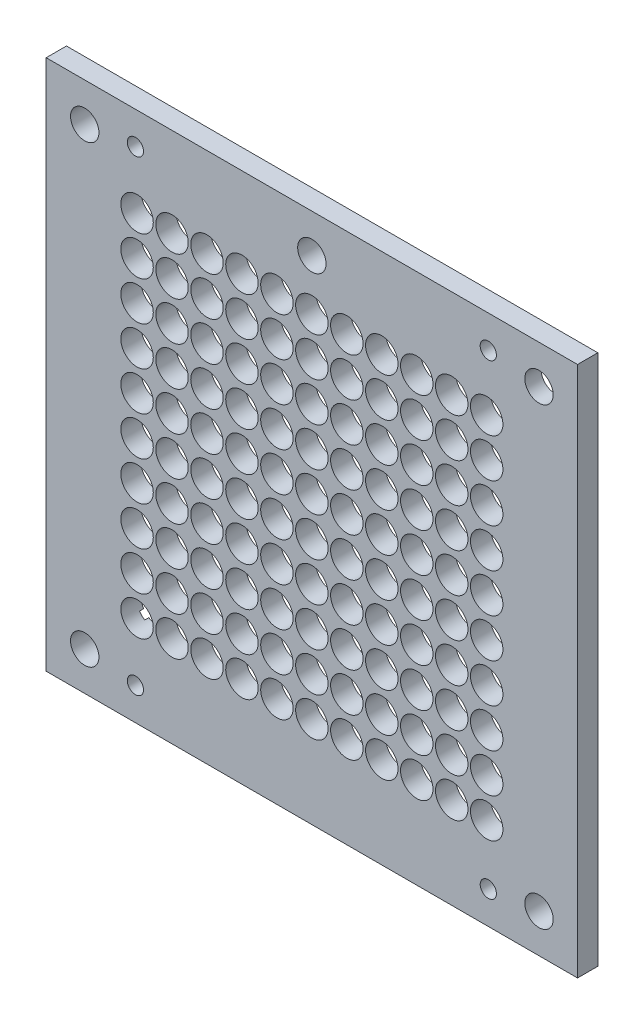
SolidWorks part; units mm, degrees
ref_plane "Ebene vorne" through (0, 0, 0) normal (0, 0, 1) x (1, 0, 0)
ref_plane "Ebene oben" through (0, 0, 0) normal (0, 1, 0) x (1, 0, 0)
ref_plane "Ebene rechts" through (0, 0, 0) normal (1, 0, 0) x (0, 0, -1)
sketch "Skizze2" plane through (0, 0, 0) normal (0, 0, 1) x (1, 0, 0)
  line L0 (-65.5, 65.5) -> (-65.5, -65.5) construction
  line L1 (-65.5, -65.5) -> (65.5, -65.5) construction
  line L2 (65.5, 65.5) -> (-65.5, 65.5) construction
  line L3 (65.5, -65.5) -> (65.5, 65.5) construction
  line L4 (-65.5, 65.5) -> (-65.5, -65.5)
  line L5 (-65.5, -65.5) -> (65.5, -65.5)
  line L6 (65.5, 65.5) -> (-65.5, 65.5)
  line L7 (65.5, -65.5) -> (65.5, 65.5)
extrude "Aufsatz-Linear austragen1" add sketch "Skizze2" along normal blind 5
sketch "Skizze3" plane through (0, 0, 0) normal (0, 0, -1) x (-1, 0, 0)
  line L0 (0, 65.5) -> (0, 0) construction
  line L1 (-65.5, 65.5) -> (65.5, 65.5) construction
  line L2 (-67.5, 67.5) -> (67.5, 67.5) construction
  circle A0 centre (0, 56) radius 3.5
  dimension "D1" = 7
  dimension "D2" = 11.5
extrude "Schnitt-Linear austragen1" cut sketch "Skizze3" against normal up to surface (5 mm away) up to face at (0, 0, 5)
sketch "Skizze4" plane through (0, 0, 0) normal (0, 0, -1) x (-1, 0, 0)
  line L0 (0, 0) -> (0, 65.5) construction
  line L1 (-65.5, 65.5) -> (65.5, 65.5) construction
  line L2 (-67.5, 67.5) -> (67.5, 67.5) construction
  circle A0 centre (0, 43.5) radius 4
  dimension "D1" = 8
  dimension "D2" = 24
extrude "Schnitt-Linear austragen2" cut sketch "Skizze4" against normal up to surface (5 mm away) up to face at (3.5, 56, 5)
pattern_linear "Lineares Muster1" count 6 spacing 8.62 along (1, 0, 0) count 10 spacing 9.6111 along (0, -1, 0) of "Schnitt-Linear austragen2"
pattern_linear "Lineares Muster2" count 6 spacing 8.62 along (-1, 0, 0) count 10 spacing 9.6111 along (0, -1, 0) skipping (0, 1), (0, 2), (0, 3), (0, 4), (0, 5), (0, 6), (0, 7), (0, 8), (0, 9) of "Schnitt-Linear austragen2"
sketch "Skizze5" plane through (0, 0, 0) normal (0, 0, -1) x (-1, 0, 0)
  line L0 (-67.5, -67.5) -> (-67.5, 67.5) construction
  line L1 (-67.5, 67.5) -> (67.5, 67.5) construction
  line L2 (67.5, 67.5) -> (67.5, -67.5) construction
  line L3 (67.5, -67.5) -> (-67.5, -67.5) construction
  circle A0 centre (-50, 50) radius 6
  circle A1 centre (50, 50) radius 6
  circle A2 centre (-50, -50) radius 6
  circle A3 centre (50, -50) radius 6
  dimension "D1" = 12
  dimension "D3" = 17.5
  dimension "D4" = 12
  dimension "D5" = 17.5
  dimension "D6" = 17.5
  dimension "D7" = 12
  dimension "D8" = 12
  dimension "D9" = 17.5
  dimension "D10" = 17.5
  dimension "D11" = 17.5
  dimension "D12" = 17.5
  dimension "D2" = 17.5
extrude "Schnitt-Linear austragen3" cut sketch "Skizze5" against normal blind 1
sketch "Skizze6" plane through (0, 0, 0) normal (0, 0, -1) x (-1, 0, 0)
  line L0 (-67.5, -67.5) -> (-67.5, 67.5) construction
  line L1 (-67.5, 67.5) -> (67.5, 67.5) construction
  line L2 (67.5, -67.5) -> (-67.5, -67.5) construction
  line L3 (67.5, 67.5) -> (67.5, -67.5) construction
  circle A0 centre (-56, 56) radius 3.5
  circle A1 centre (-56, -56) radius 3.5
  circle A2 centre (56, -56) radius 3.5
  circle A3 centre (56, 56) radius 3.5
  dimension "D1" = 7
  dimension "D2" = 11.5
  dimension "D3" = 11.5
  dimension "D4" = 7
  dimension "D5" = 7
  dimension "D6" = 7
  dimension "D7" = 11.5
  dimension "D8" = 11.5
  dimension "D9" = 11.5
  dimension "D11" = 11.5
  dimension "D12" = 11.5
  dimension "D10" = 11.5
extrude "Schnitt-Linear austragen4" cut sketch "Skizze6" against normal up to surface (5 mm away) up to face at (-39.1, -43, 5)
sketch "Skizze7" plane through (0, 0, 1) normal (0, 0, -1) x (-1, 0, 0)
  circle A0 centre (-50, 50) radius 3
  circle A1 centre (50, 50) radius 3
  circle A2 centre (50, -50) radius 3
  circle A3 centre (-50, -50) radius 3
extrude "Schnitt-Linear austragen5" cut sketch "Skizze7" against normal blind 1.2
hole_wizard "Ø4.0 (4) Durchmesser Bohrung2" positions "Skizze10" profile "Skizze11" hole size "Ø4.0" standard "DIN"
sketch "Skizze10" plane through (0, 0, 5) normal (0, 0, 1) x (1, 0, 0)
  point P0 (-43.5, 57.5)
  point P3 (43.5, 57.5)
  point P6 (43.5, -57.5)
  point P9 (-43.5, -57.5)
sketch "Skizze11" plane through (-43.5, 57.5, 5) normal (1, 0, 0) x (0, -1, 0)
  line L0 (0, 0) -> (0, 11.2017)
  line L1 (0, 11.2017) -> (2, 10)
  line L2 (2, 10) -> (2, 0)
  line L3 (2, 0) -> (0, 0)
  line L4 (0, 11.2017) -> (-2, 10) construction
  line L5 (0, -6.35) -> (0, 107.95) construction
  dimension "Bohrerdurchmesser" = 4
  dimension "Bohrungstiefe" = 10
  dimension "Spitzenwinkel" = 118
